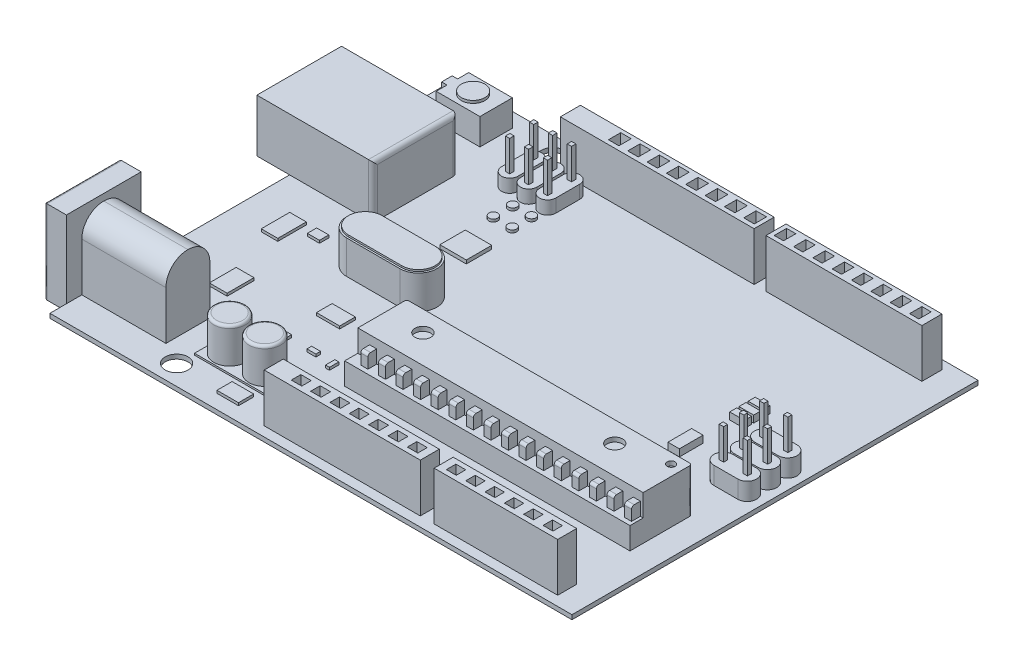
SolidWorks part; units mm, degrees
ref_plane "Front Plane" through (0, 0, 0) normal (0, 0, 1) x (1, 0, 0)
ref_plane "Top Plane" through (0, 0, 0) normal (0, 1, 0) x (1, 0, 0)
ref_plane "Right Plane" through (0, 0, 0) normal (1, 0, 0) x (0, 0, -1)
sketch "Sketch1" plane through (0, 0, 0) normal (0, 1, 0) x (1, 0, 0)
  line L0 (99, 231) -> (495, 231) construction
ref_plane "Plane1" through (0, 100, 0) normal (0, 1, 0) x (1, 0, 0)
sketch "Sketch2" plane through (0, 100, 0) normal (0, 1, 0) x (1, 0, 0)
  line L0 (406.2485, 32.6469) -> (410.391, 32.6469)
  line L1 (232.8531, 32.6469) -> (406.2485, 32.6469)
  line L2 (232.8531, 32.6469) -> (232.8531, 11.0076)
  line L3 (232.8531, 11.0076) -> (406.2485, 11.0076)
  line L5 (410.391, 32.6469) -> (410.391, 11.0076)
  line L6 (410.391, 11.0076) -> (406.2485, 11.0076)
extrude "Boss-Extrude2" add sketch "Sketch2" along normal blind 55
sketch "Sketch3" plane through (0, 100, 0) normal (0, 1, 0) x (1, 0, 0)
  line L0 (410.391, 32.6469) -> (232.8531, 32.6469) construction
  line L1 (426.2106, 32.6469) -> (566.7256, 32.6469)
  line L2 (426.2106, 32.6469) -> (426.2106, 11.0076)
  line L3 (426.2106, 11.0076) -> (566.7256, 11.0076)
  line L4 (566.7256, 32.6469) -> (566.7256, 11.0076)
  line L5 (232.8531, 11.0076) -> (410.391, 11.0076) construction
extrude "Boss-Extrude3" add sketch "Sketch3" along normal blind 55 separate body
sketch "Sketch4" plane through (0, 100, 0) normal (0, 1, 0) x (1, 0, 0)
  line L0 (258.1323, 27.3712) -> (269.983, 27.3712)
  line L5 (269.983, 27.3712) -> (269.983, 16.5363)
  line L6 (269.983, 16.5363) -> (258.1323, 16.5363)
  line L7 (258.1323, 16.5363) -> (258.1323, 27.3712)
  line L8 (280.1323, 16.5363) -> (280.1323, 27.3712)
  line L9 (280.1323, 27.3712) -> (291.983, 27.3712)
  line L10 (291.983, 16.5363) -> (280.1323, 16.5363)
  line L11 (291.983, 27.3712) -> (291.983, 16.5363)
  line L12 (302.1323, 16.5363) -> (302.1323, 27.3712)
  line L13 (302.1323, 27.3712) -> (313.983, 27.3712)
  line L14 (313.983, 16.5363) -> (302.1323, 16.5363)
  line L15 (313.983, 27.3712) -> (313.983, 16.5363)
  line L16 (324.1323, 16.5363) -> (324.1323, 27.3712)
  line L17 (324.1323, 27.3712) -> (335.983, 27.3712)
  line L18 (335.983, 16.5363) -> (324.1323, 16.5363)
  line L19 (335.983, 27.3712) -> (335.983, 16.5363)
  line L20 (346.1323, 16.5363) -> (346.1323, 27.3712)
  line L21 (346.1323, 27.3712) -> (357.983, 27.3712)
  line L22 (357.983, 16.5363) -> (346.1323, 16.5363)
  line L23 (357.983, 27.3712) -> (357.983, 16.5363)
  line L24 (368.1323, 16.5363) -> (368.1323, 27.3712)
  line L25 (368.1323, 27.3712) -> (379.983, 27.3712)
  line L26 (379.983, 16.5363) -> (368.1323, 16.5363)
  line L27 (379.983, 27.3712) -> (379.983, 16.5363)
  line L28 (390.1323, 16.5363) -> (390.1323, 27.3712)
  line L29 (390.1323, 27.3712) -> (401.983, 27.3712)
  line L30 (401.983, 16.5363) -> (390.1323, 16.5363)
  line L31 (401.983, 27.3712) -> (401.983, 16.5363)
  line L32 (434.5905, 27.3712) -> (445.7945, 27.3712)
  line L33 (445.7945, 27.3712) -> (445.7945, 16.5363)
  line L34 (445.7945, 16.5363) -> (434.5905, 16.5363)
  line L35 (434.5905, 16.5363) -> (434.5905, 27.3712)
  line L36 (456.5905, 16.5363) -> (456.5905, 27.3712)
  line L37 (456.5905, 27.3712) -> (467.7945, 27.3712)
  line L38 (467.7945, 27.3712) -> (467.7945, 16.5363)
  line L39 (467.7945, 16.5363) -> (456.5905, 16.5363)
  line L40 (478.5905, 16.5363) -> (478.5905, 27.3712)
  line L41 (478.5905, 27.3712) -> (489.7945, 27.3712)
  line L42 (489.7945, 27.3712) -> (489.7945, 16.5363)
  line L43 (489.7945, 16.5363) -> (478.5905, 16.5363)
  line L44 (500.5905, 16.5363) -> (500.5905, 27.3712)
  line L45 (500.5905, 27.3712) -> (511.7945, 27.3712)
  line L46 (511.7945, 27.3712) -> (511.7945, 16.5363)
  line L47 (511.7945, 16.5363) -> (500.5905, 16.5363)
  line L48 (522.5905, 16.5363) -> (522.5905, 27.3712)
  line L49 (522.5905, 27.3712) -> (533.7945, 27.3712)
  line L50 (533.7945, 27.3712) -> (533.7945, 16.5363)
  line L51 (533.7945, 16.5363) -> (522.5905, 16.5363)
  line L52 (544.5905, 16.5363) -> (544.5905, 27.3712)
  line L53 (544.5905, 27.3712) -> (555.7945, 27.3712)
  line L54 (555.7945, 27.3712) -> (555.7945, 16.5363)
  line L55 (555.7945, 16.5363) -> (544.5905, 16.5363)
  dimension "D1" = 7
  dimension "D2" = 6
extrude "Cut-Extrude1" cut sketch "Sketch4" along normal blind 50 from offset 5
sketch "Sketch5" plane through (0, 100, 0) normal (0, 1, 0) x (1, 0, 0)
  line L1 (151.8134, 451.812) -> (372.2687, 451.812)
  line L2 (151.8134, 451.812) -> (151.8134, 428.9817)
  line L3 (151.8134, 428.9817) -> (372.2687, 428.9817)
  line L4 (372.2687, 451.812) -> (372.2687, 428.9817)
extrude "Boss-Extrude4" add sketch "Sketch5" along normal blind 55 separate body
sketch "Sketch6" plane through (0, 100, 0) normal (0, 1, 0) x (1, 0, 0)
  line L0 (372.2687, 451.812) -> (151.8134, 451.812) construction
  line L1 (385.742, 451.812) -> (563.1714, 451.812)
  line L2 (385.742, 451.812) -> (385.742, 428.9817)
  line L3 (385.742, 428.9817) -> (563.1714, 428.9817)
  line L4 (563.1714, 451.812) -> (563.1714, 428.9817)
  line L5 (151.8134, 428.9817) -> (372.2687, 428.9817) construction
extrude "Boss-Extrude5" add sketch "Sketch6" along normal blind 55 separate body
sketch "Sketch7" plane through (0, 100, 0) normal (0, 1, 0) x (1, 0, 0)
  line L0 (201.7231, 447.7471) -> (213.6594, 447.7471)
  line L1 (213.6594, 447.7471) -> (213.6594, 433.7449)
  line L2 (213.6594, 433.7449) -> (201.7231, 433.7449)
  line L3 (201.7231, 433.7449) -> (201.7231, 447.7471)
  line L4 (223.7231, 433.7449) -> (223.7231, 447.7471)
  line L5 (235.6594, 447.7471) -> (235.6594, 433.7449)
  line L6 (235.6594, 433.7449) -> (223.7231, 433.7449)
  line L7 (223.7231, 447.7471) -> (235.6594, 447.7471)
  line L8 (245.7231, 433.7449) -> (245.7231, 447.7471)
  line L9 (257.6594, 447.7471) -> (257.6594, 433.7449)
  line L10 (257.6594, 433.7449) -> (245.7231, 433.7449)
  line L11 (245.7231, 447.7471) -> (257.6594, 447.7471)
  line L12 (267.7231, 433.7449) -> (267.7231, 447.7471)
  line L13 (279.6594, 447.7471) -> (279.6594, 433.7449)
  line L14 (279.6594, 433.7449) -> (267.7231, 433.7449)
  line L15 (267.7231, 447.7471) -> (279.6594, 447.7471)
  line L16 (289.7231, 433.7449) -> (289.7231, 447.7471)
  line L17 (301.6594, 447.7471) -> (301.6594, 433.7449)
  line L18 (301.6594, 433.7449) -> (289.7231, 433.7449)
  line L19 (289.7231, 447.7471) -> (301.6594, 447.7471)
  line L20 (311.7231, 433.7449) -> (311.7231, 447.7471)
  line L21 (323.6594, 447.7471) -> (323.6594, 433.7449)
  line L22 (323.6594, 433.7449) -> (311.7231, 433.7449)
  line L23 (311.7231, 447.7471) -> (323.6594, 447.7471)
  line L24 (333.7231, 433.7449) -> (333.7231, 447.7471)
  line L25 (345.6594, 447.7471) -> (345.6594, 433.7449)
  line L26 (345.6594, 433.7449) -> (333.7231, 433.7449)
  line L27 (333.7231, 447.7471) -> (345.6594, 447.7471)
  line L28 (355.7231, 433.7449) -> (355.7231, 447.7471)
  line L29 (367.6594, 447.7471) -> (367.6594, 433.7449)
  line L30 (367.6594, 433.7449) -> (355.7231, 433.7449)
  line L31 (355.7231, 447.7471) -> (367.6594, 447.7471)
  line L32 (390.4075, 447.7471) -> (400.9504, 447.7471)
  line L33 (400.9504, 447.7471) -> (400.9504, 433.7449)
  line L34 (400.9504, 433.7449) -> (390.4075, 433.7449)
  line L35 (390.4075, 433.7449) -> (390.4075, 447.7471)
  line L36 (412.4075, 433.7449) -> (412.4075, 447.7471)
  line L37 (412.4075, 447.7471) -> (422.9504, 447.7471)
  line L38 (422.9504, 447.7471) -> (422.9504, 433.7449)
  line L39 (422.9504, 433.7449) -> (412.4075, 433.7449)
  line L40 (434.4075, 433.7449) -> (434.4075, 447.7471)
  line L41 (434.4075, 447.7471) -> (444.9504, 447.7471)
  line L42 (444.9504, 447.7471) -> (444.9504, 433.7449)
  line L43 (444.9504, 433.7449) -> (434.4075, 433.7449)
  line L44 (456.4075, 433.7449) -> (456.4075, 447.7471)
  line L45 (456.4075, 447.7471) -> (466.9504, 447.7471)
  line L46 (466.9504, 447.7471) -> (466.9504, 433.7449)
  line L47 (466.9504, 433.7449) -> (456.4075, 433.7449)
  line L48 (478.4075, 433.7449) -> (478.4075, 447.7471)
  line L49 (478.4075, 447.7471) -> (488.9504, 447.7471)
  line L50 (488.9504, 447.7471) -> (488.9504, 433.7449)
  line L51 (488.9504, 433.7449) -> (478.4075, 433.7449)
  line L52 (500.4075, 433.7449) -> (500.4075, 447.7471)
  line L53 (500.4075, 447.7471) -> (510.9504, 447.7471)
  line L54 (510.9504, 447.7471) -> (510.9504, 433.7449)
  line L55 (510.9504, 433.7449) -> (500.4075, 433.7449)
  line L56 (522.4075, 433.7449) -> (522.4075, 447.7471)
  line L57 (522.4075, 447.7471) -> (532.9504, 447.7471)
  line L58 (532.9504, 447.7471) -> (532.9504, 433.7449)
  line L59 (532.9504, 433.7449) -> (522.4075, 433.7449)
  line L60 (544.4075, 433.7449) -> (544.4075, 447.7471)
  line L61 (544.4075, 447.7471) -> (554.9504, 447.7471)
  line L62 (554.9504, 447.7471) -> (554.9504, 433.7449)
  line L63 (554.9504, 433.7449) -> (544.4075, 433.7449)
  dimension "D1" = 8
  dimension "D2" = 8
extrude "Cut-Extrude2" cut sketch "Sketch7" along normal blind 50 from offset 5
sketch "Sketch8" plane through (0, 100, 0) normal (0, 1, 0) x (1, 0, 0)
  line L1 (239.5675, 166.433) -> (564.1861, 166.433)
  line L2 (239.5675, 166.433) -> (239.5675, 95.8017)
  line L3 (239.5675, 95.8017) -> (564.1861, 95.8017)
  line L4 (564.1861, 166.433) -> (564.1861, 95.8017)
extrude "Boss-Extrude6" add sketch "Sketch8" along normal blind 25 separate body
sketch "Sketch9" plane through (0, 125, 0) normal (0, 1, 0) x (1, 0, 0)
  line L0 (564.1861, 95.8017) -> (564.1861, 166.433) construction
  line L1 (239.5675, 166.433) -> (564.1861, 166.433)
  line L2 (239.5675, 166.433) -> (239.5675, 110.8017)
  line L3 (239.5675, 110.8017) -> (564.1861, 110.8017)
  line L4 (564.1861, 166.433) -> (564.1861, 110.8017)
  line L5 (239.5675, 95.8017) -> (564.1861, 95.8017) construction
  dimension "D1" = 15
extrude "Boss-Extrude7" add sketch "Sketch9" along normal blind 25
fillet "Fillet1" radius 3 1 edges at (239.5675, 125, -166.433)
fillet "Fillet2" radius 3 1 edges at (564.1861, 125, -166.433)
sketch "Sketch10" plane through (0, 0, -110.8017) normal (0, 0, 1) x (1, 0, 0)
  line L0 (239.5675, 125) -> (564.1861, 125) construction
  line L1 (253.0094, 140) -> (261.0094, 140)
  line L2 (253.0094, 140) -> (253.0094, 125)
  line L3 (253.0094, 125) -> (261.0094, 125)
  line L4 (261.0094, 140) -> (261.0094, 125)
  dimension "D1" = 15
  dimension "D2" = 8
extrude "Boss-Extrude8" add sketch "Sketch10" along normal blind 10
fillet "Fillet3" radius 3 1 edges at (257.0094, 140, -100.8017)
pattern_linear "LPattern1" count 16 spacing 20 along (1, 0, 0) of "Boss-Extrude8", "Fillet3"
sketch "Sketch11" plane through (0, 150, 0) normal (0, 1, 0) x (1, 0, 0)
  circle A0 centre (281.3729, 143.0171) radius 9
  circle A1 centre (499.6617, 143.0171) radius 9
  circle A2 centre (552.0412, 154.8066) radius 4.5132
  dimension "D1" = 18
  dimension "D2" = 18
extrude "Cut-Extrude3" cut sketch "Sketch11" against normal blind 5
sketch "Sketch12" plane through (0, 100, 0) normal (0, 1, 0) x (1, 0, 0)
  line L0 (547.5175, 264.7495) -> (574.6286, 264.7495) construction
  line L1 (547.5175, 275.4513) -> (574.6286, 275.4513)
  line L2 (547.5175, 254.0478) -> (574.6286, 254.0478)
  line L3 (547.5175, 241.7495) -> (574.6286, 241.7495) construction
  line L4 (547.5175, 252.4513) -> (574.6286, 252.4513)
  line L5 (547.5175, 231.0478) -> (574.6286, 231.0478)
  line L6 (547.5175, 218.7495) -> (574.6286, 218.7495) construction
  line L7 (547.5175, 229.4513) -> (574.6286, 229.4513)
  line L8 (547.5175, 208.0478) -> (574.6286, 208.0478)
  arc A0 (547.5175, 275.4513) -> (547.5175, 254.0478) centre (547.5175, 264.7495) ccw
  arc A1 (574.6286, 254.0478) -> (574.6286, 275.4513) centre (574.6286, 264.7495) ccw
  arc A2 (547.5175, 252.4513) -> (547.5175, 231.0478) centre (547.5175, 241.7495) ccw
  arc A3 (574.6286, 231.0478) -> (574.6286, 252.4513) centre (574.6286, 241.7495) ccw
  arc A4 (547.5175, 229.4513) -> (547.5175, 208.0478) centre (547.5175, 218.7495) ccw
  arc A5 (574.6286, 208.0478) -> (574.6286, 229.4513) centre (574.6286, 218.7495) ccw
  point P2 (561.0731, 264.7495)
  point P10 (561.0731, 241.7495)
  point P17 (561.0731, 218.7495)
  dimension "D1" = 3
extrude "Boss-Extrude9" add sketch "Sketch12" along normal blind 20 separate body
sketch "Sketch13" plane through (0, 120, 0) normal (0, 1, 0) x (1, 0, 0)
  line L0 (545.0175, 243.9932) -> (550.0175, 243.9932)
  line L1 (545.0175, 266.9932) -> (550.0175, 266.9932)
  line L2 (545.0175, 266.9932) -> (545.0175, 262.5059)
  line L3 (545.0175, 262.5059) -> (550.0175, 262.5059)
  line L4 (550.0175, 266.9932) -> (550.0175, 262.5059)
  line L5 (545.0175, 266.9932) -> (550.0175, 262.5059) construction
  line L6 (545.0175, 262.5059) -> (550.0175, 266.9932) construction
  line L7 (572.1286, 266.9932) -> (577.1286, 266.9932)
  line L8 (572.1286, 266.9932) -> (572.1286, 262.5059)
  line L9 (572.1286, 262.5059) -> (577.1286, 262.5059)
  line L10 (577.1286, 266.9932) -> (577.1286, 262.5059)
  line L11 (572.1286, 266.9932) -> (577.1286, 262.5059) construction
  line L12 (572.1286, 262.5059) -> (577.1286, 266.9932) construction
  line L13 (545.0175, 243.9932) -> (545.0175, 239.5059)
  line L14 (545.0175, 239.5059) -> (550.0175, 239.5059)
  line L15 (550.0175, 243.9932) -> (550.0175, 239.5059)
  line L16 (572.1286, 243.9932) -> (572.1286, 239.5059)
  line L17 (572.1286, 243.9932) -> (577.1286, 243.9932)
  line L18 (572.1286, 239.5059) -> (577.1286, 239.5059)
  line L19 (577.1286, 243.9932) -> (577.1286, 239.5059)
  line L20 (545.0175, 220.9932) -> (550.0175, 220.9932)
  line L21 (545.0175, 220.9932) -> (545.0175, 216.5059)
  line L22 (545.0175, 216.5059) -> (550.0175, 216.5059)
  line L23 (550.0175, 220.9932) -> (550.0175, 216.5059)
  line L24 (572.1286, 220.9932) -> (572.1286, 216.5059)
  line L25 (572.1286, 220.9932) -> (577.1286, 220.9932)
  line L26 (572.1286, 216.5059) -> (577.1286, 216.5059)
  line L27 (577.1286, 220.9932) -> (577.1286, 216.5059)
  point P0 (547.5175, 264.7495)
  point P6 (574.6286, 264.7495)
  dimension "D1" = 5
  dimension "D2" = 5
  dimension "D3" = 3
extrude "Boss-Extrude10" add sketch "Sketch13" along normal blind 35
sketch "Sketch14" plane through (0, 100, 0) normal (0, 1, 0) x (1, 0, 0)
  line L1 (486.6022, 243.5044) -> (499.6563, 243.5044)
  line L2 (486.6022, 243.5044) -> (486.6022, 216.5804)
  line L3 (486.6022, 216.5804) -> (499.6563, 216.5804)
  line L4 (499.6563, 243.5044) -> (499.6563, 216.5804)
  line L5 (486.6022, 243.5044) -> (499.6563, 216.5804) construction
  line L6 (486.6022, 216.5804) -> (499.6563, 243.5044) construction
  point P0 (493.1293, 230.0424)
extrude "Boss-Extrude11" add sketch "Sketch14" along normal blind 8 separate body
sketch "Sketch15" plane through (0, 100, 0) normal (0, 1, 0) x (1, 0, 0)
  line L1 (491.9055, 310.6026) -> (508.631, 310.6026)
  line L2 (491.9055, 310.6026) -> (491.9055, 302.6026)
  line L3 (491.9055, 302.6026) -> (508.631, 302.6026)
  line L4 (508.631, 310.6026) -> (508.631, 302.6026)
  line L5 (491.9055, 300.1026) -> (508.631, 300.1026)
  line L6 (491.9055, 300.1026) -> (491.9055, 292.1026)
  line L7 (491.9055, 292.1026) -> (508.631, 292.1026)
  line L8 (508.631, 300.1026) -> (508.631, 292.1026)
  line L9 (491.9055, 289.6026) -> (508.631, 289.6026)
  line L10 (491.9055, 289.6026) -> (491.9055, 281.6026)
  line L11 (491.9055, 281.6026) -> (508.631, 281.6026)
  line L12 (508.631, 289.6026) -> (508.631, 281.6026)
  dimension "D1" = 8
  dimension "D2" = 8
  dimension "D3" = 8
  dimension "D4" = 2.5
  dimension "D5" = 2.5
extrude "Boss-Extrude12" add sketch "Sketch15" along normal blind 8 separate body
sketch "Sketch16" plane through (0, 100, 0) normal (0, 1, 0) x (1, 0, 0)
  line L0 (136.8418, 413.6852) -> (136.8418, 386.3944) construction
  line L1 (146.172, 413.6852) -> (146.172, 386.3944)
  line L2 (127.5116, 413.6852) -> (127.5116, 386.3944)
  line L3 (158.3418, 413.6852) -> (158.3418, 386.3944) construction
  line L4 (167.672, 413.6852) -> (167.672, 386.3944)
  line L5 (149.0116, 413.6852) -> (149.0116, 386.3944)
  line L6 (179.8418, 413.6852) -> (179.8418, 386.3944) construction
  line L7 (189.172, 413.6852) -> (189.172, 386.3944)
  line L8 (170.5116, 413.6852) -> (170.5116, 386.3944)
  arc A0 (146.172, 413.6852) -> (127.5116, 413.6852) centre (136.8418, 413.6852) ccw
  arc A1 (127.5116, 386.3944) -> (146.172, 386.3944) centre (136.8418, 386.3944) ccw
  arc A2 (167.672, 413.6852) -> (149.0116, 413.6852) centre (158.3418, 413.6852) ccw
  arc A3 (149.0116, 386.3944) -> (167.672, 386.3944) centre (158.3418, 386.3944) ccw
  arc A4 (189.172, 413.6852) -> (170.5116, 413.6852) centre (179.8418, 413.6852) ccw
  arc A5 (170.5116, 386.3944) -> (189.172, 386.3944) centre (179.8418, 386.3944) ccw
  point P2 (136.8418, 400.0398)
  point P10 (158.3418, 400.0398)
  point P17 (179.8418, 400.0398)
  dimension "D1" = 3
extrude "Boss-Extrude13" add sketch "Sketch16" along normal blind 15 separate body
sketch "Sketch17" plane through (0, 115, 0) normal (0, 1, 0) x (1, 0, 0)
  line L0 (155.9448, 388.8944) -> (160.7388, 388.8944)
  line L1 (134.4448, 416.1852) -> (139.2388, 416.1852)
  line L2 (134.4448, 416.1852) -> (134.4448, 411.1852)
  line L3 (134.4448, 411.1852) -> (139.2388, 411.1852)
  line L4 (139.2388, 416.1852) -> (139.2388, 411.1852)
  line L5 (134.4448, 416.1852) -> (139.2388, 411.1852) construction
  line L6 (134.4448, 411.1852) -> (139.2388, 416.1852) construction
  line L7 (134.4448, 388.8944) -> (139.2388, 388.8944)
  line L8 (134.4448, 388.8944) -> (134.4448, 383.8944)
  line L9 (134.4448, 383.8944) -> (139.2388, 383.8944)
  line L10 (139.2388, 388.8944) -> (139.2388, 383.8944)
  line L11 (134.4448, 388.8944) -> (139.2388, 383.8944) construction
  line L12 (134.4448, 383.8944) -> (139.2388, 388.8944) construction
  line L13 (155.9448, 388.8944) -> (155.9448, 383.8944)
  line L14 (155.9448, 383.8944) -> (160.7388, 383.8944)
  line L15 (160.7388, 388.8944) -> (160.7388, 383.8944)
  line L16 (155.9448, 411.1852) -> (160.7388, 411.1852)
  line L17 (155.9448, 416.1852) -> (160.7388, 416.1852)
  line L18 (160.7388, 416.1852) -> (160.7388, 411.1852)
  line L19 (155.9448, 416.1852) -> (155.9448, 411.1852)
  line L20 (177.4448, 388.8944) -> (182.2388, 388.8944)
  line L21 (177.4448, 388.8944) -> (177.4448, 383.8944)
  line L22 (177.4448, 383.8944) -> (182.2388, 383.8944)
  line L23 (182.2388, 388.8944) -> (182.2388, 383.8944)
  line L24 (177.4448, 411.1852) -> (182.2388, 411.1852)
  line L25 (177.4448, 416.1852) -> (182.2388, 416.1852)
  line L26 (182.2388, 416.1852) -> (182.2388, 411.1852)
  line L27 (177.4448, 416.1852) -> (177.4448, 411.1852)
  point P0 (136.8418, 413.6852)
  point P6 (136.8418, 386.3944)
  dimension "D1" = 5
  dimension "D2" = 5
  dimension "D3" = 3
extrude "Boss-Extrude14" add sketch "Sketch17" along normal blind 35
sketch "Sketch18" plane through (0, 100, 0) normal (0, 1, 0) x (1, 0, 0)
  circle A0 centre (159.0143, 367.571) radius 5
  circle A1 centre (180.3105, 367.571) radius 5
  dimension "D1" = 10
  dimension "D2" = 10
extrude "Boss-Extrude15" add sketch "Sketch18" along normal blind 3 separate body
sketch "Sketch19" plane through (0, 100, 0) normal (0, 1, 0) x (1, 0, 0)
  circle A0 centre (158.9108, 345.6157) radius 5
  circle A1 centre (180.4006, 345.6157) radius 5
  dimension "D1" = 10
  dimension "D2" = 10
extrude "Boss-Extrude16" add sketch "Sketch19" along normal blind 3 separate body
sketch "Sketch20" plane through (0, 100, 0) normal (0, 1, 0) x (1, 0, 0)
  line L1 (158.2506, 314.3814) -> (188.3208, 314.3814)
  line L2 (158.2506, 314.3814) -> (158.2506, 285.4353)
  line L3 (158.2506, 285.4353) -> (188.3208, 285.4353)
  line L4 (188.3208, 314.3814) -> (188.3208, 285.4353)
extrude "Boss-Extrude17" add sketch "Sketch20" along normal blind 4 separate body
sketch "Sketch21" plane through (0, 100, 0) normal (0, 1, 0) x (1, 0, 0)
  line L0 (132.6768, 226.138) -> (193.0983, 226.138) construction
  line L1 (132.6768, 247.2153) -> (193.0983, 247.2153)
  line L2 (132.6768, 205.0608) -> (193.0983, 205.0608)
  arc A0 (132.6768, 247.2153) -> (132.6768, 205.0608) centre (132.6768, 226.138) ccw
  arc A1 (193.0983, 205.0608) -> (193.0983, 247.2153) centre (193.0983, 226.138) ccw
  point P2 (162.8876, 226.138)
extrude "Boss-Extrude18" add sketch "Sketch21" along normal blind 38 separate body
sketch "Sketch22" plane through (0, 138, 0) normal (0, 1, 0) x (1, 0, 0)
  line L4 (132.6768, 207.0608) -> (193.0983, 207.0608)
  line L5 (193.0983, 245.2153) -> (132.6768, 245.2153)
  line L6 (132.6768, 207.0608) -> (193.0983, 207.0608)
  line L7 (193.0983, 245.2153) -> (132.6768, 245.2153)
  arc A4 (132.6768, 245.2153) -> (132.6768, 207.0608) centre (132.6768, 226.138) ccw
  arc A5 (193.0983, 207.0608) -> (193.0983, 245.2153) centre (193.0983, 226.138) ccw
  arc A6 (132.6768, 245.2153) -> (132.6768, 207.0608) centre (132.6768, 226.138) ccw
  arc A7 (193.0983, 207.0608) -> (193.0983, 245.2153) centre (193.0983, 226.138) ccw
  dimension "D1" = 2
extrude "Boss-Extrude19" add sketch "Sketch22" along normal blind 2
sketch "Sketch23" plane through (0, 100, 0) normal (0, 1, 0) x (1, 0, 0)
  line L1 (153.9538, 167.1464) -> (180.3513, 167.1464)
  line L2 (153.9538, 167.1464) -> (153.9538, 149.3102)
  line L3 (153.9538, 149.3102) -> (180.3513, 149.3102)
  line L4 (180.3513, 167.1464) -> (180.3513, 149.3102)
extrude "Boss-Extrude20" add sketch "Sketch23" along normal blind 3 separate body
sketch "Sketch24" plane through (0, 100, 0) normal (0, 1, 0) x (1, 0, 0)
  line L1 (153.1434, 113.4833) -> (161.5743, 113.4833)
  line L2 (153.1434, 113.4833) -> (153.1434, 102.8042)
  line L3 (153.1434, 102.8042) -> (161.5743, 102.8042)
  line L4 (161.5743, 113.4833) -> (161.5743, 102.8042)
  line L5 (184.3377, 113.4833) -> (194.4548, 113.4833)
  line L6 (184.3377, 113.4833) -> (184.3377, 108.1437)
  line L7 (184.3377, 108.1437) -> (194.4548, 108.1437)
  line L8 (194.4548, 113.4833) -> (194.4548, 108.1437)
  line L9 (210.7545, 113.4833) -> (215.251, 113.4833)
  line L10 (210.7545, 113.4833) -> (210.7545, 102.8042)
  line L11 (210.7545, 102.8042) -> (215.251, 102.8042)
  line L12 (215.251, 113.4833) -> (215.251, 102.8042)
extrude "Boss-Extrude21" add sketch "Sketch24" along normal blind 3 separate body
sketch "Sketch25" plane through (0, 100, 0) normal (0, 1, 0) x (1, 0, 0)
  line L1 (123.6278, 80.8259) -> (203.6278, 80.8259)
  line L2 (123.6278, 80.8259) -> (123.6278, 40.9226)
  line L3 (123.6278, 40.9226) -> (203.6278, 40.9226)
  line L4 (203.6278, 80.8259) -> (203.6278, 40.9226)
  dimension "D1" = 80
extrude "Boss-Extrude22" add sketch "Sketch25" along normal blind 2 separate body
sketch "Sketch26" plane through (0, 102, 0) normal (0, 1, 0) x (1, 0, 0)
  line L0 (203.6278, 40.9226) -> (203.6278, 80.8259) construction
  line L1 (123.6278, 80.8259) -> (123.6278, 40.9226) construction
  circle A0 centre (143.6278, 60.8743) radius 18
  circle A1 centre (183.6278, 60.8743) radius 18
  dimension "D1" = 36
  dimension "D2" = 36
  dimension "D3" = 20
  dimension "D4" = 20
extrude "Boss-Extrude23" add sketch "Sketch26" along normal blind 40
fillet "Fillet4" radius 3 2 edges at (143.6278, 142, -42.8743) (183.6278, 142, -42.8743)
sketch "Sketch27" plane through (0, 100, 0) normal (0, 1, 0) x (1, 0, 0)
  line L1 (173.8923, 33.417) -> (198.3841, 33.417)
  line L2 (173.8923, 33.417) -> (173.8923, 16.1562)
  line L3 (173.8923, 16.1562) -> (198.3841, 16.1562)
  line L4 (198.3841, 33.417) -> (198.3841, 16.1562)
extrude "Boss-Extrude24" add sketch "Sketch27" along normal blind 3 separate body
sketch "Sketch28" plane through (0, 100, 0) normal (0, 1, 0) x (1, 0, 0)
  line L1 (-37.2502, 369.0521) -> (94.7376, 369.0521)
  line L2 (-37.2502, 369.0521) -> (-37.2502, 272.7367)
  line L3 (-37.2502, 272.7367) -> (94.7376, 272.7367)
  line L4 (94.7376, 369.0521) -> (94.7376, 272.7367)
extrude "Boss-Extrude25" add sketch "Sketch28" along normal blind 60 separate body
sketch "Sketch29" plane through (-37.2502, 0, 0) normal (-1, 0, 0) x (0, 0, 1)
  line L6 (-359.0521, 143.6242) -> (-341.0521, 150.1652)
  line L7 (-341.0521, 150.1652) -> (-300.7367, 150.1652)
  line L8 (-300.7367, 150.1652) -> (-282.7367, 143.6242)
  line L9 (-282.7367, 110) -> (-282.7367, 160)
  line L10 (-359.0521, 110) -> (-282.7367, 110)
  line L11 (-359.0521, 160) -> (-359.0521, 110)
  line L12 (-282.7367, 110) -> (-282.7367, 143.6242)
  line L13 (-359.0521, 110) -> (-282.7367, 110)
  line L14 (-359.0521, 143.6242) -> (-359.0521, 110)
  dimension "D2" = 18
  dimension "D3" = 18
  dimension "D1" = 10
extrude "Cut-Extrude4" cut sketch "Sketch29" against normal blind 80
sketch "Sketch30" plane through (42.7498, 0, 0) normal (-1, 0, 0) x (0, 0, 1)
  line L1 (-342.958, 136.3049) -> (-302.9442, 136.3049)
  line L2 (-342.958, 136.3049) -> (-342.958, 121.8855)
  line L3 (-342.958, 121.8855) -> (-302.9442, 121.8855)
  line L4 (-302.9442, 136.3049) -> (-302.9442, 121.8855)
  line L5 (-342.958, 136.3049) -> (-302.9442, 121.8855) construction
  line L6 (-342.958, 121.8855) -> (-302.9442, 136.3049) construction
  point P0 (-322.9511, 129.0952)
extrude "Boss-Extrude26" add sketch "Sketch30" along normal blind 80
fillet "Fillet5" radius 5 5 edges at (94.7376, 160, -320.8944) (94.7376, 130, -369.0521) (94.7376, 130, -272.7367) (-37.2502, 126.8121, -359.0521) (-37.2502, 126.8121, -282.7367)
sketch "Sketch31" plane through (0, 100, 0) normal (0, 1, 0) x (1, 0, 0)
  line L0 (31.0074, 445.4587) -> (80.7545, 445.4587)
  line L1 (80.7545, 445.4587) -> (80.7545, 408.5177)
  line L2 (80.7545, 408.5177) -> (31.0074, 408.5177)
  line L3 (31.0074, 408.5177) -> (31.0074, 420.8314)
  line L4 (31.0074, 420.8314) -> (24.8506, 420.8314)
  line L5 (24.8506, 420.8314) -> (24.8506, 432.8987)
  line L6 (24.8506, 432.8987) -> (31.0074, 432.8987)
  line L7 (31.0074, 432.8987) -> (31.0074, 445.4587)
extrude "Boss-Extrude27" add sketch "Sketch31" along normal blind 30 separate body
sketch "Sketch32" plane through (0, 130, 0) normal (0, 1, 0) x (1, 0, 0)
  circle A0 centre (54.5785, 426.9882) radius 13.3549
extrude "Boss-Extrude28" add sketch "Sketch32" along normal blind 3
sketch "Sketch33" plane through (0, 100, 0) normal (0, 1, 0) x (1, 0, 0)
  line L1 (0, 36.281) -> (95.7081, 36.281)
  line L2 (0, 36.281) -> (0, 86.281)
  line L3 (0, 86.281) -> (95.7081, 86.281)
  line L4 (95.7081, 36.281) -> (95.7081, 86.281)
  dimension "D1" = 50
extrude "Boss-Extrude29" add sketch "Sketch33" along normal blind 80 separate body
sketch "Sketch34" plane through (0, 0, 0) normal (-1, 0, 0) x (0, 0, 1)
  line L0 (-86.281, 140) -> (-36.281, 140) construction
  line L1 (-86.281, 180) -> (-86.281, 100) construction
  line L2 (-36.281, 180) -> (-36.281, 100) construction
  line L4 (-103.781, 187.5) -> (-18.781, 187.5)
  line L5 (-103.781, 187.5) -> (-103.781, 92.5)
  line L6 (-103.781, 92.5) -> (-18.781, 92.5)
  line L7 (-18.781, 187.5) -> (-18.781, 92.5)
  line L8 (-103.781, 187.5) -> (-18.781, 92.5) construction
  line L9 (-103.781, 92.5) -> (-18.781, 187.5) construction
  point P6 (-61.281, 140)
  dimension "D1" = 85
  dimension "D2" = 95
extrude "Boss-Extrude30" add sketch "Sketch34" along normal blind 25
fillet "Fillet6" radius 25 2 edges at (47.854, 180, -86.281) (47.854, 180, -36.281)
sketch "Sketch35" plane through (-25, 0, 0) normal (-1, 0, 0) x (0, 0, 1)
  circle A0 centre (-61.281, 139.1841) radius 21.698
extrude "Cut-Extrude5" cut sketch "Sketch35" against normal blind 97
fillet "Fillet7" radius 3 4 edges at (-25, 92.5, -61.281) (-25, 140, -103.781) (-25, 140, -18.781) (-25, 187.5, -61.281)
sketch "Sketch36" plane through (0, 100, 0) normal (0, 1, 0) x (1, 0, 0)
  line L1 (39.9665, 232.8832) -> (58.7981, 232.8832)
  line L2 (39.9665, 232.8832) -> (39.9665, 200.4928)
  line L3 (39.9665, 200.4928) -> (58.7981, 200.4928)
  line L4 (58.7981, 232.8832) -> (58.7981, 200.4928)
  line L5 (70.6334, 232.8832) -> (84.4161, 232.8832)
  line L6 (70.6334, 232.8832) -> (70.6334, 222.2829)
  line L7 (70.6334, 222.2829) -> (84.4161, 222.2829)
  line L8 (84.4161, 232.8832) -> (84.4161, 222.2829)
extrude "Boss-Extrude31" add sketch "Sketch36" along normal blind 3 separate body
sketch "Sketch37" plane through (0, 100, 0) normal (0, 1, 0) x (1, 0, 0)
  line L1 (63.7421, 148.2013) -> (83.9854, 148.2013)
  line L2 (63.7421, 148.2013) -> (63.7421, 117.6211)
  line L3 (63.7421, 117.6211) -> (83.9854, 117.6211)
  line L4 (83.9854, 148.2013) -> (83.9854, 117.6211)
extrude "Boss-Extrude32" add sketch "Sketch37" along normal blind 3 separate body
sketch "Sketch39" plane through (0, 100, 0) normal (0, 1, 0) x (1, 0, 0)
  line L1 (0, 0) -> (594, 0)
  line L2 (0, 0) -> (0, 462)
  line L3 (0, 462) -> (594, 462)
  line L4 (594, 0) -> (594, 462)
  dimension "D1" = 594
  dimension "D2" = 462
extrude "Boss-Extrude33" add sketch "Sketch39" against normal blind 5
sketch "Sketch38" plane through (0, 100, 0) normal (0, 1, 0) x (1, 0, 0)
  circle A0 centre (132.4115, 439.8756) radius 13.537
  circle A1 centre (121.4771, 22.6691) radius 12.9867
extrude "Cut-Extrude6" cut sketch "Sketch38" against normal through all
